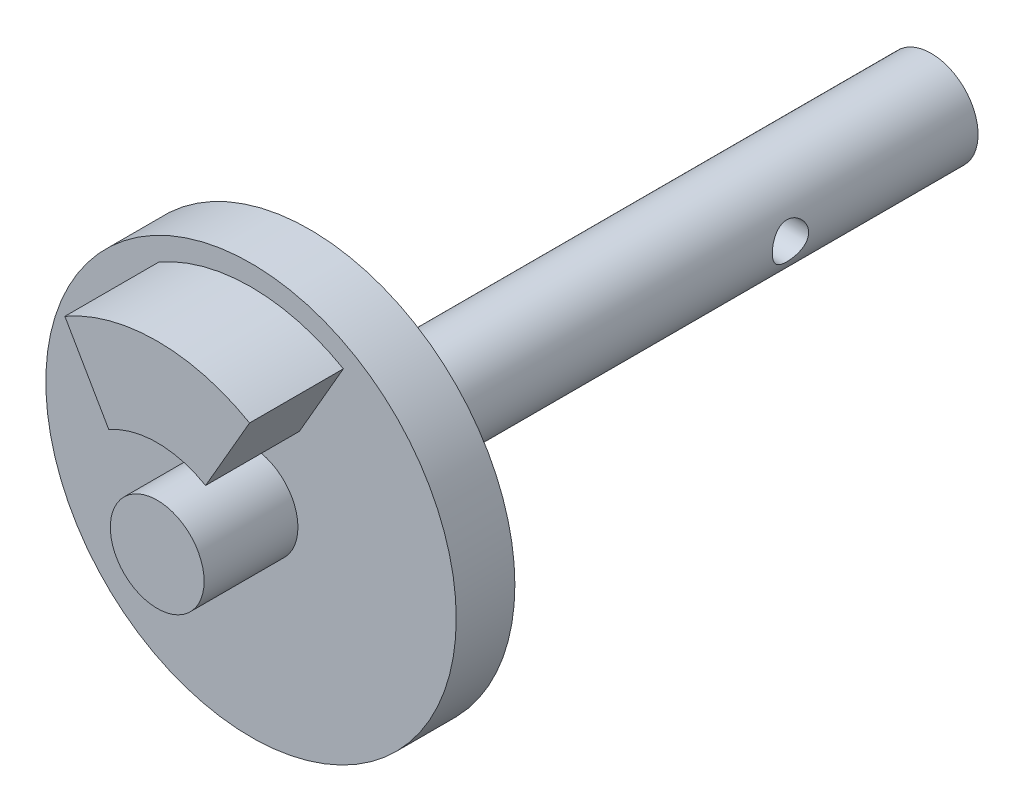
SolidWorks part; units mm, degrees
ref_plane "Front Plane" through (0, 0, 0) normal (0, 0, 1) x (1, 0, 0)
ref_plane "Top Plane" through (0, 0, 0) normal (0, 1, 0) x (1, 0, 0)
ref_plane "Right Plane" through (0, 0, 0) normal (1, 0, 0) x (0, 0, -1)
sketch "Sketch1" plane through (0, 0, 0) normal (0, 0, 1) x (1, 0, 0)
  circle A0 centre (0, 0) radius 17.5
  dimension "D1" = 35
extrude "Boss-Extrude1" add sketch "Sketch1" along normal mid plane 5
sketch "Sketch2" plane through (0, 0, 2.5) normal (0, 0, 1) x (1, 0, 0)
  line L3 (0, 0) -> (0, 11) construction
  line L4 (7.875, 13.6399) -> (4.125, 7.1447)
  line L5 (-4.125, 7.1447) -> (-7.875, 13.6399)
  arc A1 (4.125, 7.1447) -> (-4.125, 7.1447) centre (0, 0) ccw
  arc A6 (-7.875, 13.6399) -> (7.875, 13.6399) centre (0, 0) cw
  circle A7 centre (0, 0) radius 17.5 construction
  dimension "D2" = 7.5
  dimension "D3" = 1.75
  dimension "D1" = 30
extrude "Boss-Extrude2" add sketch "Sketch2" along normal blind 8
sketch "Sketch3" plane through (0, 0, 2.5) normal (0, 0, 1) x (1, 0, 0)
  circle A0 centre (0, 0) radius 4
extrude "Boss-Extrude3" add sketch "Sketch3" along normal blind 8
sketch "Sketch7" plane through (0, 0, -2.5) normal (0, 0, -1) x (-1, 0, 0)
  circle A0 centre (0, 0) radius 4
extrude "Boss-Extrude4" add sketch "Sketch7" along normal blind 53
ref_axis "Axis1" through (0, 0, -55.5) along (0, 0, 1)
ref_plane "Plane1" through (0, 0, 0) normal (-1, 0, 0) x (0, 0, 1)
sketch "Sketch8" plane through (0, 0, 0) normal (-1, 0, 0) x (0, 0, 1)
  line L0 (-55.5, 0) -> (-39.5, 0) construction
  line L1 (-55.5, 4) -> (-55.5, -4) construction
  line L2 (-55.5, 0) -> (-2.5, 0) construction
  circle A0 centre (-39.5, 0) radius 1.55
extrude "Cut-Extrude1" cut sketch "Sketch8" against normal up to surface and the other way up to surface up to face at (-4, 0, -55.5) other way up to face at (-4, 0, -55.5)
